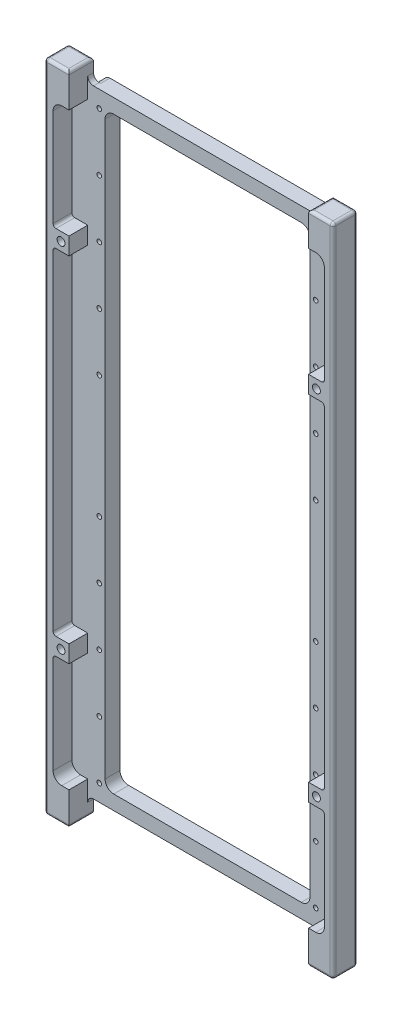
SolidWorks part; units mm, degrees
ref_plane "Front Plane" through (0, 0, 0) normal (0, 0, 1) x (1, 0, 0)
ref_plane "Top Plane" through (0, 0, 0) normal (0, 1, 0) x (1, 0, 0)
ref_plane "Right Plane" through (0, 0, 0) normal (1, 0, 0) x (0, 0, -1)
sketch "Sketch1" plane through (0, 0, 0) normal (0, 1, 0) x (1, 0, 0)
  line L1 (41.5, -4.25) -> (50, -4.25)
  line L2 (41.5, -4.25) -> (41.5, 4.25)
  line L3 (41.5, 4.25) -> (50, 4.25)
  line L4 (50, -4.25) -> (50, 4.25)
  line L5 (41.5, -4.25) -> (50, 4.25) construction
  line L6 (41.5, 4.25) -> (50, -4.25) construction
  point P0 (45.75, 0)
  dimension "D1" = 8.5
  dimension "D2" = 8.5
  dimension "D3" = 50
extrude "Boss-Extrude1" add sketch "Sketch1" along normal blind 227
sketch "Sketch2" plane through (41.5, 0, 0) normal (-1, 0, 0) x (0, 0, 1)
  line L0 (-4.25, 227) -> (-4.25, 0) construction
  line L1 (-4.25, 220.5) -> (-2.25, 220.5)
  line L2 (-4.25, 220.5) -> (-4.25, 6.5)
  line L3 (-4.25, 6.5) -> (-2.25, 6.5)
  line L4 (-2.25, 220.5) -> (-2.25, 6.5)
  line L5 (-4.25, 227) -> (4.25, 227) construction
  line L6 (-4.25, 0) -> (4.25, 0) construction
  point P6 (0, 227)
  dimension "D1" = 2
  dimension "D2" = 6.5
  dimension "D3" = 6.5
extrude "Boss-Extrude2" add sketch "Sketch2" along normal blind 50
mirror "Mirror2" about plane through (0, 0, 0) normal (1, 0, 0) of "Boss-Extrude1", "Boss-Extrude2"
sketch "Sketch3" plane through (0, 0, -4.25) normal (0, 0, -1) x (-1, 0, 0)
  line L0 (41.5, 220.5) -> (-41.5, 220.5) construction
  line L1 (-39, 6.5) -> (39, 6.5)
  line L2 (-41, 8.5) -> (-41, 218.5)
  line L3 (-39, 220.5) -> (39, 220.5)
  line L4 (41, 8.5) -> (41, 218.5)
  line L5 (-41, 6.5) -> (41, 220.5) construction
  line L6 (-41, 220.5) -> (41, 6.5) construction
  arc A0 (-39, 6.5) -> (-41, 8.5) centre (-39, 8.5) cw
  arc A1 (39, 6.5) -> (41, 8.5) centre (39, 8.5) ccw
  arc A2 (-41, 218.5) -> (-39, 220.5) centre (-39, 218.5) cw
  arc A3 (39, 220.5) -> (41, 218.5) centre (39, 218.5) cw
  point P0 (0, 113.5)
  dimension "D3" = 2
  dimension "D1" = 82
  dimension "D2" = 214
extrude "Boss-Extrude3" add sketch "Sketch3" along normal blind 3.18
sketch "Sketch4" plane through (0, 0, -7.43) normal (0, 0, -1) x (-1, 0, 0)
  line L0 (-39, 6.5) -> (39, 6.5) construction
  line L1 (-32.5, 11.5) -> (32.5, 11.5)
  line L2 (-35.5, 14.5) -> (-35.5, 212.5)
  line L3 (-32.5, 215.5) -> (32.5, 215.5)
  line L4 (35.5, 14.5) -> (35.5, 212.5)
  line L5 (-35.5, 11.5) -> (35.5, 215.5) construction
  line L6 (-35.5, 215.5) -> (35.5, 11.5) construction
  line L7 (39, 220.5) -> (-39, 220.5) construction
  line L8 (-41, 218.5) -> (-41, 8.5) construction
  line L9 (41, 8.5) -> (41, 218.5) construction
  arc A0 (-32.5, 11.5) -> (-35.5, 14.5) centre (-32.5, 14.5) cw
  arc A1 (32.5, 11.5) -> (35.5, 14.5) centre (32.5, 14.5) ccw
  arc A2 (32.5, 215.5) -> (35.5, 212.5) centre (32.5, 212.5) cw
  arc A3 (-35.5, 212.5) -> (-32.5, 215.5) centre (-32.5, 212.5) cw
  point P0 (0, 113.5)
  dimension "D1" = 3
  dimension "D2" = 5
  dimension "D3" = 5
  dimension "D4" = 5.5
  dimension "D5" = 5.5
extrude "Cut-Extrude1" cut sketch "Sketch4" against normal through all
fillet "Fillet1" radius 2 4 edges
fillet "Fillet2" radius 1 20 edges at (50, 113.5, -4.25) (50, 113.5, 4.25) (-50, 113.5, -4.25) (-50, 113.5, 4.25) (45.75, 0, -4.25) (50, 0, 0) (45.75, 0, 4.25) (41.5, 0, 0) (-41.5, 0, 0) (-45.75, 0, -4.25) (-50, 0, 0) (-45.75, 0, 4.25) (45.75, 227, 4.25) (50, 227, 0) (45.75, 227, -4.25) (41.5, 227, 0) (-41.5, 227, 0) (-45.75, 227, -4.25) (-50, 227, 0) (-45.75, 227, 4.25)
sketch "Sketch5" plane through (0, 0, 4.25) normal (0, 0, 1) x (1, 0, 0)
  line L0 (-39.5, 220.5) -> (39.5, 220.5) construction
  line L1 (-44, 11.5) -> (44, 11.5)
  line L2 (-47, 14.5) -> (-47, 48.3)
  line L3 (-44, 215.5) -> (44, 215.5)
  line L4 (47, 14.5) -> (47, 48.3)
  line L5 (-47, 11.5) -> (47, 215.5) construction
  line L6 (-47, 215.5) -> (47, 11.5) construction
  line L7 (-47, 113.5) -> (47, 113.5) construction
  line L8 (-46, 177.7) -> (-41.5, 177.7)
  line L9 (46, 171.7) -> (41.5, 171.7)
  line L10 (-46, 171.7) -> (-41.5, 171.7)
  line L11 (-41.5, 177.7) -> (-41.5, 171.7)
  line L14 (0, 215.5) -> (0, 11.5) construction
  line L15 (-47, 178.7) -> (-47, 212.5)
  line L16 (41.5, 177.7) -> (41.5, 171.7)
  line L17 (46, 177.7) -> (41.5, 177.7)
  line L18 (47, 178.7) -> (47, 212.5)
  line L19 (46, 49.3) -> (41.5, 49.3)
  line L20 (41.5, 49.3) -> (41.5, 55.3)
  line L21 (46, 55.3) -> (41.5, 55.3)
  line L22 (-46, 49.3) -> (-41.5, 49.3)
  line L23 (-41.5, 49.3) -> (-41.5, 55.3)
  line L24 (-46, 55.3) -> (-41.5, 55.3)
  line L25 (-47, 56.3) -> (-47, 170.7)
  line L26 (47, 56.3) -> (47, 170.7)
  arc A0 (-44, 11.5) -> (-47, 14.5) centre (-44, 14.5) cw
  arc A1 (44, 11.5) -> (47, 14.5) centre (44, 14.5) ccw
  arc A2 (44, 215.5) -> (47, 212.5) centre (44, 212.5) cw
  arc A3 (-47, 212.5) -> (-44, 215.5) centre (-44, 212.5) cw
  arc A4 (-46, 177.7) -> (-47, 178.7) centre (-46, 178.7) cw
  arc A5 (-47, 170.7) -> (-46, 171.7) centre (-46, 170.7) cw
  arc A6 (46, 177.7) -> (47, 178.7) centre (46, 178.7) ccw
  arc A7 (46, 171.7) -> (47, 170.7) centre (46, 170.7) cw
  arc A8 (46, 49.3) -> (47, 48.3) centre (46, 48.3) cw
  arc A9 (46, 55.3) -> (47, 56.3) centre (46, 56.3) ccw
  arc A10 (-46, 49.3) -> (-47, 48.3) centre (-46, 48.3) ccw
  arc A11 (-46, 55.3) -> (-47, 56.3) centre (-46, 56.3) cw
  point P0 (0, 113.5)
  point P42 (-47, 177.7)
  point P45 (-47, 171.7)
  point P48 (47, 177.7)
  point P51 (47, 171.7)
  point P54 (47, 49.3)
  point P57 (47, 55.3)
  point P60 (-47, 49.3)
  point P63 (-47, 55.3)
  dimension "D4" = 3
  dimension "D9" = 1
  dimension "D1" = 94
  dimension "D2" = 204
  dimension "D3" = 5
  dimension "D5" = 37.8
  dimension "D6" = 6
  dimension "D7" = 5.5
  dimension "D8" = 102
extrude "Cut-Extrude2" cut sketch "Sketch5" against normal blind 6.5
hole_wizard "M2x0.4 Tapped Hole1" positions "Sketch7" profile "Sketch6" tap size "M2x0.4" standard "ANSI Metric" end condition through all
sketch "Sketch7" plane through (0, 0, -7.43) normal (0, 0, -1) x (-1, 0, 0)
  line L0 (39, 220.5) -> (-39, 220.5) construction
  line L1 (-41, 218.5) -> (-41, 8.5) construction
  line L2 (-35.5, 113.5) -> (35.5, 113.5) construction
  line L3 (-35.5, 212.5) -> (-35.5, 14.5) construction
  line L4 (35.5, 14.5) -> (35.5, 212.5) construction
  point P0 (-37.5, 214.7)
  point P15 (37.5, 214.7)
  point P16 (37.5, 194.7)
  point P17 (37.5, 174.7)
  point P18 (37.5, 154.7)
  point P19 (37.5, 134.7)
  point P20 (-37.5, 194.7)
  point P21 (-37.5, 174.7)
  point P22 (-37.5, 154.7)
  point P23 (-37.5, 134.7)
  point P32 (-37.5, 12.3)
  point P33 (-37.5, 32.3)
  point P34 (-37.5, 52.3)
  point P35 (-37.5, 72.3)
  point P36 (-37.5, 92.3)
  point P37 (37.5, 92.3)
  point P38 (37.5, 72.3)
  point P39 (37.5, 52.3)
  point P40 (37.5, 32.3)
  point P41 (37.5, 12.3)
  dimension "D1" = 5.8
  dimension "D2" = 3.5
  dimension "D3" = 2
  dimension "D4" = 5
sketch "Sketch6" plane through (37.5, 214.7, -7.43) normal (1, 0, 0) x (0, 1, 0)
  line L0 (0, 0) -> (0, 11.68)
  line L1 (0, 11.68) -> (0.8, 11.68)
  line L2 (0.8, 11.68) -> (0.8, 0)
  line L5 (0.8, 0) -> (0, 0)
  line L11 (0, -6.35) -> (0, 107.95) construction
  dimension "Thread Major Dia." = 1.6
  dimension "Thru Tap Drill Depth" = 11.68
sketch "Sketch8" plane through (0, 0, -4.25) normal (0, 0, -1) x (-1, 0, 0)
  line L0 (-49, 227) -> (-42.5, 227) construction
  line L1 (-50, 1) -> (-50, 226) construction
  circle A0 centre (-44.25, 174.7) radius 1.375
  dimension "D1" = 2.75
  dimension "D2" = 52.3
  dimension "D3" = 5.75
extrude "Cut-Extrude3" cut sketch "Sketch8" against normal through all
sketch "Sketch9" plane through (0, 0, -4.25) normal (0, 0, -1) x (-1, 0, 0)
  circle A0 centre (-44.25, 174.7) radius 2.5
  dimension "D1" = 5
extrude "Cut-Extrude4" cut sketch "Sketch9" against normal blind 4.75
pattern_linear "LPattern1" count 2 spacing 88.5 along (-1, 0, 0) count 2 spacing 122.4 along (0, -1, 0) of "Cut-Extrude4", "Cut-Extrude3"
